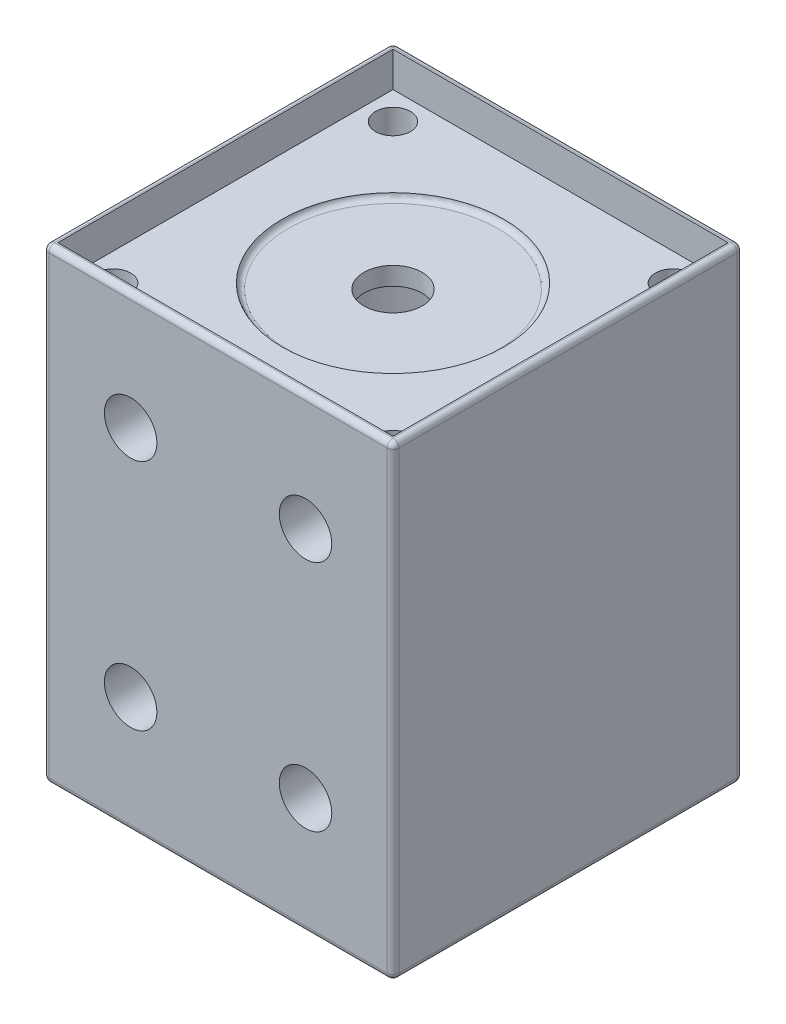
SolidWorks part; units mm, degrees
material "3.0255 (EN-AW 1350A)"
ref_plane "Płaszczyzna przednia" through (0, 0, 0) normal (0, 0, 1) x (1, 0, 0)
ref_plane "Płaszczyzna górna" through (0, 0, 0) normal (0, 1, 0) x (1, 0, 0)
ref_plane "Płaszczyzna prawa" through (0, 0, 0) normal (1, 0, 0) x (0, 0, -1)
sketch "Szkic1" plane through (0, 0, 0) normal (0, 1, 0) x (1, 0, 0)
  line L1 (30, -30) -> (-30, -30)
  line L2 (30, -30) -> (30, 30)
  line L3 (30, 30) -> (-30, 30)
  line L4 (-30, -30) -> (-30, 30)
  line L5 (30, -30) -> (-30, 30) construction
  line L6 (30, 30) -> (-30, -30) construction
  point P0 (0, 0)
  dimension "D1" = 60
  dimension "D2" = 60
extrude "Dodanie-wyciągnięcie1" add sketch "Szkic1" along normal blind 80
sketch "Szkic2" plane through (0, 80, 0) normal (0, 1, 0) x (1, 0, 0)
  line L1 (-28.75, -28.75) -> (28.75, -28.75)
  line L2 (-28.75, -28.75) -> (-28.75, 28.75)
  line L3 (-28.75, 28.75) -> (28.75, 28.75)
  line L4 (28.75, -28.75) -> (28.75, 28.75)
  line L5 (-28.75, -28.75) -> (28.75, 28.75) construction
  line L6 (-28.75, 28.75) -> (28.75, -28.75) construction
  point P0 (0, 0)
  dimension "D1" = 57.5
  dimension "D2" = 57.5
extrude "Wytnij-wyciągnięcie1" cut sketch "Szkic2" against normal blind 6
sketch "Szkic3" plane through (0, 74, 0) normal (0, 1, 0) x (1, 0, 0)
  circle A0 centre (0, 0) radius 5
  dimension "D1" = 10
extrude "Wytnij-wyciągnięcie2" cut sketch "Szkic3" against normal blind 24
sketch "Szkic4" plane through (0, 74, 0) normal (0, 1, 0) x (1, 0, 0)
  circle A0 centre (0, 0) radius 19
  dimension "D1" = 38
extrude "Wytnij-wyciągnięcie3" cut sketch "Szkic4" against normal blind 0.9
fillet "Zaokrąglenie1" radius 1 1 edges at (0, 73.1, 19)
sketch "Szkic5" plane through (0, 74, 0) normal (0, 1, 0) x (1, 0, 0)
  line L2 (0, -55) -> (0, 55) construction
  line L3 (-55, 0) -> (55, 0) construction
  line L4 (30, 30) -> (-30, 30) construction
  line L5 (-30, 30) -> (-30, -30) construction
  circle A0 centre (-24, 24) radius 3
  circle A1 centre (24, 24) radius 3
  circle A2 centre (24, -24) radius 3
  circle A3 centre (-24, -24) radius 3
  dimension "D1" = 6
  dimension "D2" = 6
  dimension "D3" = 6
hole_wizard "Otwory ustalające Ø6.0mm1" positions "Szkic6" profile "Szkic7" hole size "Ø6.0" standard "ISO" end condition through all
sketch "Szkic6" plane through (0, 74, 0) normal (0, 1, 0) x (1, 0, 0)
  point P0 (-24, 24)
  point P3 (24, 24)
  point P6 (24, -24)
  point P9 (-24, -24)
sketch "Szkic7" plane through (-24, 74, -24) normal (1, 0, 0) x (0, 0, 1)
  line L0 (0, 0) -> (0, 74)
  line L1 (0, 74) -> (3, 74)
  line L2 (3, 74) -> (3, 0)
  line L5 (3, 0) -> (0, 0)
  line L11 (0, -6.35) -> (0, 107.95) construction
  dimension "Średnica otworu na wylot" = 6
  dimension "Głębokość otworu na wylot" = 74
sketch "Szkic8" plane through (0, 0, 0) normal (0, -1, 0) x (1, 0, 0)
  circle A0 centre (0, 0) radius 21
  dimension "D1" = 42
extrude "Wytnij-wyciągnięcie5" cut sketch "Szkic8" against normal blind 70
fillet "Zaokrąglenie2" radius 1 12 edges at (0, 80, 30) (30, 40, 30) (30, 80, 0) (-30, 80, 0) (-30, 40, 30) (30, 40, -30) (0, 80, -30) (-30, 40, -30) (0, 0, 30) (30, 0, 0) (-30, 0, 0) (0, 0, -30)
sketch "Szkic9" plane through (0, 0, -30) normal (0, 0, -1) x (-1, 0, 0)
  line L0 (-15, 116.6784) -> (-15, -11.4858) construction
  line L1 (-60.8132, 20) -> (51.3545, 20) construction
  line L2 (-71.606, 60) -> (65.8091, 60) construction
  line L3 (15, 116.6784) -> (15, -11.4858) construction
  line L4 (-29, 80) -> (29, 80) construction
  line L5 (30, 79) -> (30, 1) construction
  dimension "D1" = 40
  dimension "D2" = 30
  dimension "D3" = 20
  dimension "D4" = 15
hole_wizard "Otwór pod śrubę M81" positions "Szkic10" profile "Szkic11" hole size "M8" standard "ISO"
sketch "Szkic10" plane through (0, 0, -30) normal (0, 0, -1) x (-1, 0, 0)
  line L0 (-15, 116.6784) -> (-15, -11.4858) construction
  line L1 (-71.606, 60) -> (65.8091, 60) construction
  line L2 (15, 116.6784) -> (15, -11.4858) construction
  line L3 (-60.8132, 20) -> (51.3545, 20) construction
  point P0 (-15, 60)
  point P6 (15, 60)
  point P10 (15, 20)
  point P14 (-15, 20)
sketch "Szkic11" plane through (15, 60, -30) normal (1, 0, 0) x (0, 1, 0)
  line L0 (0, 0) -> (0, 12.7039)
  line L1 (0, 12.7039) -> (4.5, 10)
  line L2 (4.5, 10) -> (4.5, 0)
  line L5 (4.5, 0) -> (0, 0)
  line L10 (0, 12.7039) -> (-4.5, 10) construction
  line L11 (0, -6.35) -> (0, 107.95) construction
  dimension "Średnica otworu" = 9
  dimension "Głębokość otworu" = 10
  dimension "Kąt wiertła" = 118
mirror "Lustro1" about plane through (0, 0, 0) normal (0, 0, 1) of "Otwór pod śrubę M81"
